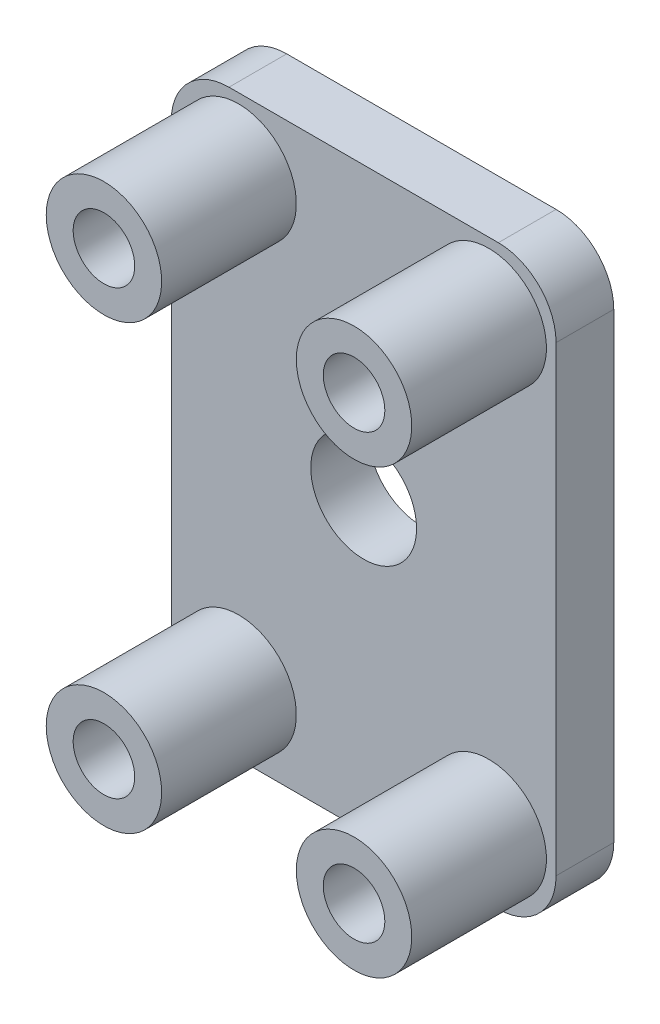
SolidWorks part; units mm, degrees
ref_plane "Front Plane" through (0, 0, 0) normal (0, 0, 1) x (1, 0, 0)
ref_plane "Top Plane" through (0, 0, 0) normal (0, 1, 0) x (1, 0, 0)
ref_plane "Right Plane" through (0, 0, 0) normal (1, 0, 0) x (0, 0, -1)
sketch "Sketch1" plane through (0, 0, 0) normal (0, 0, 1) x (1, 0, 0)
  line L1 (-10, -15) -> (10, -15)
  line L2 (-10, -15) -> (-10, 15)
  line L3 (-10, 15) -> (10, 15)
  line L4 (10, -15) -> (10, 15)
  line L5 (-10, -15) -> (10, 15) construction
  line L6 (-10, 15) -> (10, -15) construction
  point P0 (0, 0)
  dimension "D1" = 30
  dimension "D2" = 20
extrude "Boss-Extrude1" add sketch "Sketch1" along normal blind 3
hole_wizard "Ø3.2 (3.2) Diameter Hole1" positions "Sketch4" profile "Sketch3" hole size "Ø3.2" standard "ANSI Metric" end condition through all
sketch "Sketch4" plane through (0, 0, 3) normal (0, 0, 1) x (1, 0, 0)
  line L0 (-10, 15) -> (-10, -15) construction
  line L1 (10, 15) -> (-10, 15) construction
  line L2 (10, -15) -> (10, 15) construction
  line L3 (-10, -15) -> (10, -15) construction
  point P0 (-6.5, 11.5)
  point P2 (6.5, 11.5)
  point P4 (6.5, -11.5)
  point P6 (-6.5, -11.5)
  dimension "D1" = 3.5
  dimension "D2" = 3.5
  dimension "D3" = 3.5
  dimension "D4" = 3.5
  dimension "D5" = 3.5
  dimension "D6" = 3.5
  dimension "D7" = 3.5
  dimension "D8" = 3.5
sketch "Sketch3" plane through (-6.5, 11.5, 3) normal (1, 0, 0) x (0, -1, 0)
  line L0 (0, 0) -> (0, 3)
  line L1 (0, 3) -> (1.6, 3)
  line L2 (1.6, 3) -> (1.6, 0)
  line L5 (1.6, 0) -> (0, 0)
  line L11 (0, -6.35) -> (0, 107.95) construction
  dimension "Thru Hole Dia." = 3.2
  dimension "Thru Hole Depth" = 3
sketch "Sketch5" plane through (0, 0, 3) normal (0, 0, 1) x (1, 0, 0)
  circle A0 centre (-6.5, 11.5) radius 1.6
  circle A1 centre (-6.5, 11.5) radius 3
  circle A2 centre (6.5, 11.5) radius 1.6
  circle A3 centre (6.5, 11.5) radius 3
  circle A4 centre (6.5, -11.5) radius 1.6
  circle A5 centre (6.5, -11.5) radius 3
  circle A6 centre (-6.5, -11.5) radius 1.6
  circle A7 centre (-6.5, -11.5) radius 3
extrude "Boss-Extrude2" add sketch "Sketch5" along normal blind 20
sketch "Sketch6" plane through (0, 0, 3) normal (0, 0, 1) x (1, 0, 0)
  circle A0 centre (0, 0) radius 2.75
  dimension "D1" = 5.5
extrude "Cut-Extrude1" cut sketch "Sketch6" against normal through all
sketch "Sketch7" plane through (10, 0, 0) normal (1, 0, 0) x (0, 0, -1)
  line L0 (-10, 0) -> (0, 0) construction
  line L1 (-10, 20) -> (-30, 20)
  line L2 (-10, 20) -> (-10, -20)
  line L3 (-10, -20) -> (-30, -20)
  line L4 (-30, 20) -> (-30, -20)
  dimension "D1" = 10
  dimension "D2" = 40
  dimension "D3" = 20
extrude "Cut-Extrude2" cut sketch "Sketch7" against normal through all
fillet "Fillet1" radius 3 4 edges at (10, -15, 1.5) (-10, -15, 1.5) (-10, 15, 1.5) (10, 15, 1.5)
